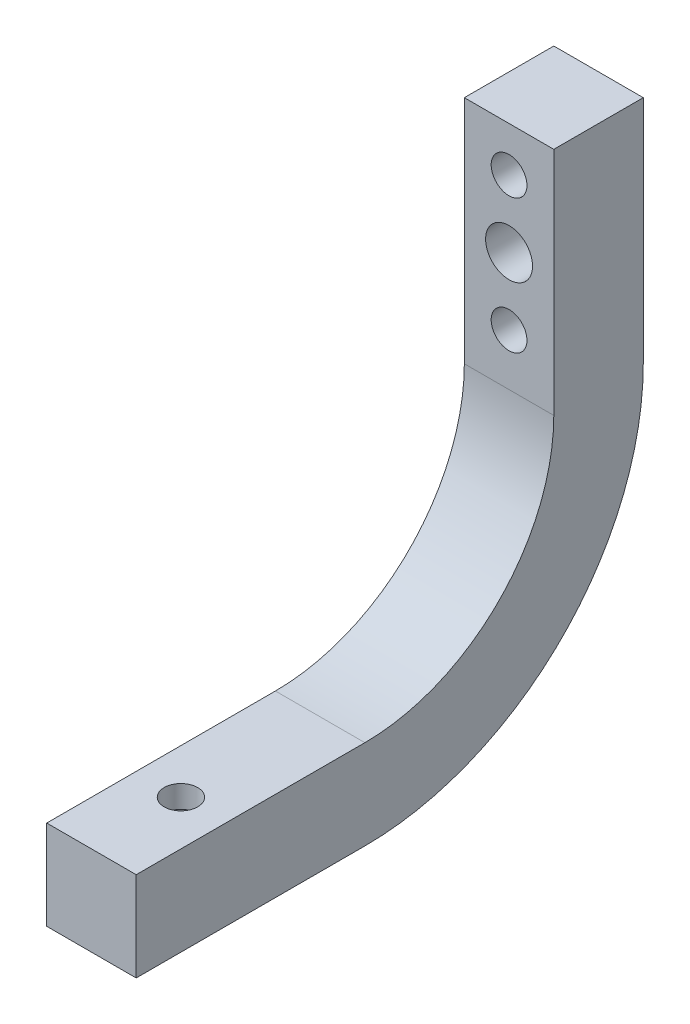
SolidWorks part; units mm, degrees
ref_plane "Front Plane" through (0, 0, 0) normal (0, 0, 1) x (1, 0, 0)
ref_plane "Top Plane" through (0, 0, 0) normal (0, 1, 0) x (1, 0, 0)
ref_plane "Right Plane" through (0, 0, 0) normal (1, 0, 0) x (0, 0, -1)
ref_axis "Z" through (0, 0, 47.607) along (0, 0, -1)
sketch "Sketch1" plane through (0, 0, 0) normal (1, 0, 0) x (0, 0, -1)
  line L0 (-8, 10) -> (0, 10)
  line L1 (0, 10) -> (0, -10.6067)
  line L2 (0, -18) -> (-17.5, -35.5) construction
  line L3 (-24.8933, -35.5) -> (-37.34, -35.5)
  line L4 (-37.34, -35.5) -> (-37.34, -27.5) construction
  line L5 (-37.34, -27.5) -> (-24.8933, -27.5)
  line L6 (-20.8137, -27.5) -> (-8, -14.6863) construction
  line L7 (-8, -10.6067) -> (-8, 10)
  line L8 (-14.4069, -21.0931) -> (-8.75, -26.75) construction
  line L9 (-24.8933, -27.5) -> (-20.8137, -27.5) construction
  line L10 (-37.34, -27.5) -> (-45.34, -27.5)
  line L11 (-37.34, -27.5) -> (-37.34, -35.5) construction
  line L12 (-37.34, -35.5) -> (-45.34, -35.5)
  line L13 (-45.34, -27.5) -> (-45.34, -35.5)
  line L14 (-8, -14.6863) -> (-8, -10.6067) construction
  line L15 (0, -10.6067) -> (0, -18) construction
  line L16 (-17.5, -35.5) -> (-24.8933, -35.5) construction
  arc A0 (-24.8933, -27.5) -> (-8, -10.6067) centre (-24.8933, -10.6067) ccw
  arc A1 (-24.8933, -35.5) -> (0, -10.6067) centre (-24.8933, -10.6067) ccw
  dimension "D2" = 37.34
  dimension "D3" = 35.5
  dimension "D4" = 10
  dimension "D5" = 135
  dimension "D6" = 17.5
  dimension "D7" = 8
  dimension "D8" = 12.4467
extrude "Boss-Extrude1" add sketch "Sketch1" along normal blind 4 and the other way blind 4
sketch "Sketch3" plane through (0, -27.5, 0) normal (0, 1, 0) x (1, 0, 0)
  line L0 (-4.4, 0) -> (4.4, 0) construction
  line L1 (0, -24.937) -> (0, 24.937) construction
  circle A0 centre (0, -37.34) radius 1.5
  dimension "D2" = 3
  dimension "D1" = 37.34
extrude "Cut-Extrude1" cut sketch "Sketch3" against normal through all
sketch "Sketch4" plane through (0, 0, 8) normal (0, 0, 1) x (1, 0, 0)
  line L0 (0, -6) -> (0, 6) construction
  circle A0 centre (0, 0) radius 2.1
  circle A1 centre (0, 6) radius 1.6
  circle A2 centre (0, -6) radius 1.6
  dimension "D1" = 4.2
  dimension "D3" = 3.2
  dimension "D2" = 12
extrude "Cut-Extrude2" cut sketch "Sketch4" against normal through all both and the other way through all
ref_axis "Axis1" through (0, -27.5, 37.34) along (0, 1, 0)
sketch "Sketch5" plane through (0, -35.5, 0) normal (0, -1, 0) x (1, 0, 0)
  circle A0 centre (0, 37.34) radius 2.275
  dimension "D1" = 4.55
extrude "Cut-Extrude3" cut sketch "Sketch5" against normal blind 6
sketch "Sketch6" plane through (0, -35.5, 0) normal (0, -1, 0) x (1, 0, 0)
  circle A0 centre (0, 37.34) radius 3.825
  dimension "D1" = 7.65
extrude "Cut-Extrude4" cut sketch "Sketch6" against normal blind 0.75
equation "\"rbracket-width\"=8"
equation "\"D1@Boss-Extrude1\"=\"rbracket-width\"/2"
equation "\"D2@Boss-Extrude1\"=\"rbracket-width\"/2"
equation "\"EyeCaptureRadius\"= ( \"EyeDiameter\" + \"EyeClearance\" ) / 2"
equation "\"rbracket_planetocenterline_dist\"= \"BasePlaneDistance\""
equation "\"D2@Sketch1\"=\"rbracket_planetocenterline_dist\""
equation "\"EyeDiameter\" = 35"
equation "\"BasePlaneDistance\" = \"EyeDiameter\"/2+19.84"
equation "\"EyeClearance\" = 2"
equation "\"D1@Sketch1\"=\"rbracket-width\""
equation "\"D3@Sketch1\"=(\"EyeDiameter\"+\"EyeClearance\"+\"EyeClearance\")/2 + \"L2Thickness\" + \"rbracket-width\""
equation "\"D4@Sketch1\"= 10"
equation "\"D6@Sketch1\"=\"EyeDiameter\"/2"
equation "\"D7@Sketch1\"=\"rbracket-width\""
equation "\"D1@Sketch3\"=\"BasePlaneDistance\""
equation "\"L2Thickness\" = 8"
equation "\"D8@Sketch1\"=\"rbracket_planetocenterline_dist\"/3"
equation "\"BearingFlangeOD\"= 7.5"
equation "\"BearingFlangeThickness\"= 0.75"
equation "\"BearingHousingID\"=4.5"
equation "\"BearingDepth\"= 6"
equation "\"D1@Sketch5\"=\"BearingHousingID\" + \"PrinterFilamentThickness\" * \"ApplyPrinterOffsets\" / 2"
equation "\"D1@Cut-Extrude3\"=\"BearingDepth\""
equation "\"D1@Sketch6\"=\"BearingFlangeOD\" + \"PrinterFilamentThickness\" * 1.5 * \"ApplyPrinterOffsets\""
equation "\"D1@Cut-Extrude4\"=\"BearingFlangeThickness\""
equation "\"PrinterFilamentThickness\"= 0.1"
equation "\"ApplyPrinterOffsets\"= 1"
